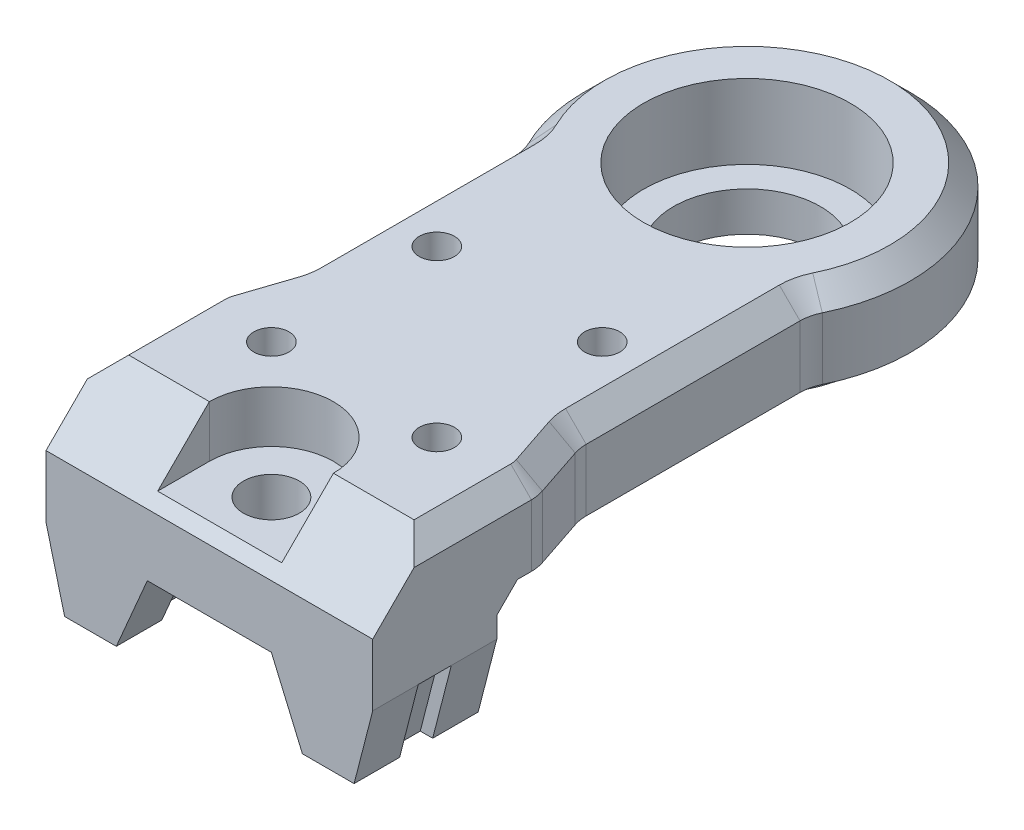
SolidWorks part; units mm, degrees
material "ABS"
ref_plane "正面" through (0, 0, 0) normal (0, 0, 1) x (1, 0, 0)
ref_plane "平面" through (0, 0, 0) normal (0, 1, 0) x (1, 0, 0)
ref_plane "右側面" through (0, 0, 0) normal (1, 0, 0) x (0, 0, -1)
sketch "ｽｹｯﾁ1" plane through (0, 0, 0) normal (0, 1, 0) x (1, 0, 0)
  line L2 (-7.9, 0) -> (-7.9, -26)
  line L3 (-7.9, -26) -> (7.9, -26)
  line L4 (7.9, 0) -> (7.9, -26)
  line L5 (-7.9, 0) -> (7.9, -26) construction
  line L6 (-7.9, -26) -> (7.9, 0) construction
  arc A0 (7.9, 0) -> (-7.9, 0) centre (0, 0) ccw
  point P7 (0, -13)
  dimension "D2" = 0
  dimension "D4" = 26
  dimension "D3" = 15.8
extrude "ﾎﾞｽ - 押し出し1" add sketch "ｽｹｯﾁ1" along normal blind 4
sketch "ｽｹｯﾁ4" plane through (0, 0, 26) normal (0, 0, 1) x (1, 0, 0)
  line L1 (-7, -5.5) -> (-4.5, -5.5)
  line L2 (-4.5, -5.5) -> (-3, -2)
  line L3 (-3, -2) -> (3, -2)
  line L4 (3, -2) -> (4.5, -5.5)
  line L5 (4.5, -5.5) -> (7, -5.5)
  line L7 (7.9, 0) -> (-7.9, 0)
  line L8 (-7, -5.5) -> (-7.9, -2)
  line L9 (-7.9, -2) -> (-7.9, 0)
  line L10 (7.9, 0) -> (7.9, -2)
  line L11 (7.9, -2) -> (7, -5.5)
  dimension "D1" = 5.5
  dimension "D2" = 3.5
  dimension "D3" = 3
  dimension "D4" = 7
  dimension "D5" = 2.5
  dimension "D9" = 2
  dimension "D10" = 2
extrude "ﾎﾞｽ - 押し出し3" add sketch "ｽｹｯﾁ4" against normal blind 6
chamfer "面取り1" distance 3 angle 45 1 edges at (0, 4, 26)
sketch "ｽｹｯﾁ5" plane through (0, 4, 0) normal (0, 1, 0) x (1, 0, 0)
  line L0 (-4, -19) -> (4, -19) construction
  line L1 (7.9, -26) -> (-7.9, -26) construction
  circle A0 centre (-4, -19) radius 0.85
  circle A1 centre (4, -19) radius 0.85
  dimension "D1" = 1.7
  dimension "D2" = 1.7
  dimension "D4" = 4
  dimension "D3" = 8
  dimension "D5" = 7
extrude "ｶｯﾄ - 押し出し1" cut sketch "ｽｹｯﾁ5" against normal blind 4
pattern_linear "直線ﾊﾟﾀｰﾝ1" count 2 spacing 8 along (0, 0, -1) of "ｶｯﾄ - 押し出し1"
sketch "ｽｹｯﾁ6" plane through (0, 4, 0) normal (0, 1, 0) x (1, 0, 0)
  line L0 (-3, -23) -> (-3, -27)
  line L1 (-3, -27) -> (3, -27)
  line L2 (3, -27) -> (3, -23)
  line L3 (7.9, -26) -> (-7.9, -26) construction
  arc A0 (3, -23) -> (-3, -23) centre (0, -23) ccw
  dimension "D1" = 6
  dimension "D3" = 3
  dimension "D2" = 0
  dimension "D4" = 4
extrude "ｶｯﾄ - 押し出し2" cut sketch "ｽｹｯﾁ6" against normal blind 2.5
sketch "ｽｹｯﾁ7" plane through (0, 1.5, 0) normal (0, 1, 0) x (1, 0, 0)
  circle A0 centre (0, -23) radius 1.35
  dimension "D1" = 2.7
extrude "ｶｯﾄ - 押し出し3" cut sketch "ｽｹｯﾁ7" against normal up to next
sketch "ｽｹｯﾁ8" plane through (0, 0, 0) normal (0, -1, 0) x (1, 0, 0)
  circle A0 centre (0, 0) radius 6
  dimension "D1" = 12
extrude "ﾎﾞｽ - 押し出し4" add sketch "ｽｹｯﾁ8" along normal blind 1.5
fillet "ﾌｨﾚｯﾄ1" radius 0.5 1 edges at (0, 0, 6)
sketch "ｽｹｯﾁ9" plane through (0, 4, 0) normal (0, 1, 0) x (1, 0, 0)
  circle A0 centre (0, 0) radius 5
  dimension "D1" = 10
extrude "ｶｯﾄ - 押し出し4" cut sketch "ｽｹｯﾁ9" against normal blind 3.6
sketch "ｽｹｯﾁ10" plane through (0, 0.4, 0) normal (0, 1, 0) x (1, 0, 0)
  circle A0 centre (0, 0) radius 3.55
  dimension "D1" = 7.1
extrude "ｶｯﾄ - 押し出し5" cut sketch "ｽｹｯﾁ10" against normal blind 3.6
ref_plane "平面1" through (0, 0, 23) normal (0, 0, 1) x (1, 0, 0)
sketch "ｽｹｯﾁ11" plane through (0, 0, 23) normal (0, 0, 1) x (1, 0, 0)
  line L0 (3, -2) -> (4.5, -5.5)
  line L1 (3, -2) -> (3.6, -2)
  line L2 (4.5, -5.5) -> (5.1, -5.5)
  line L3 (3.6, -2) -> (5.1, -5.5)
  line L4 (3, -2) -> (5.1, -5.5) construction
  line L5 (4.5, -5.5) -> (3.6, -2) construction
  line L6 (4.5, -5.5) -> (7, -5.5) construction
  line L7 (7.9, -2) -> (7, -5.5)
  line L8 (7.9, -2) -> (7.3, -2)
  line L9 (7, -5.5) -> (6.4, -5.5)
  line L10 (7.3, -2) -> (6.4, -5.5)
  line L11 (7.9, -2) -> (6.4, -5.5) construction
  line L12 (7, -5.5) -> (7.3, -2) construction
  point P5 (4.05, -3.75)
  point P14 (7.15, -3.75)
  dimension "D1" = 0.6
extrude "ｶｯﾄ - 押し出し6" cut sketch "ｽｹｯﾁ11" against normal mid plane 1.6
mirror "ﾐﾗｰ1" about plane through (0, 0, 0) normal (1, 0, 0) of "ｶｯﾄ - 押し出し6"
sketch "ｽｹｯﾁ12" plane through (0, 4, 0) normal (0, 1, 0) x (1, 0, 0)
  line L0 (-7.9, -18) -> (-6.9, -15)
  line L1 (-7.9, 0) -> (-7.9, -23) construction
  line L2 (-6.9, -15) -> (-6.9, -3.8471)
  line L3 (-7.9, -18) -> (-7.9, 0)
  line L4 (7.9, -26) -> (-7.9, -26) construction
  arc A0 (-7.9, 0) -> (-6.9, -3.8471) centre (0, 0) ccw
  arc A1 (7.9, 0) -> (-7.9, 0) centre (0, 0) ccw construction
  dimension "D1" = 6.9
  dimension "D2" = 11
  dimension "D3" = 8
extrude "ｶｯﾄ - 押し出し7" cut sketch "ｽｹｯﾁ12" against normal through all
mirror "ﾐﾗｰ2" about plane through (0, 0, 0) normal (1, 0, 0) of "ｶｯﾄ - 押し出し7"
fillet "ﾌｨﾚｯﾄ2" radius 2 6 edges at (-7.9, 2, 18) (-6.9, 2, 15) (-6.9, 2, 3.8471) (7.9, 2, 18) (6.9, 2, 15) (6.9, 2, 3.8471)
chamfer "面取り2" distance 1 angle 45 14 edges at (-7.9, 4, 20.6623) (0, 4, -7.9) (7.9, 4, 20.6623) (0, 0, 20) (-7.8742, 4, 18.0042) (-7.4, 4, 16.5) (-6.9258, 4, 14.9958) (-6.9, 4, 9.5057) (-6.9512, 4, 3.8864) (6.9512, 4, 3.8864) (6.9, 4, 9.5057) (6.9258, 4, 14.9958) (7.4, 4, 16.5) (7.8742, 4, 18.0042)
